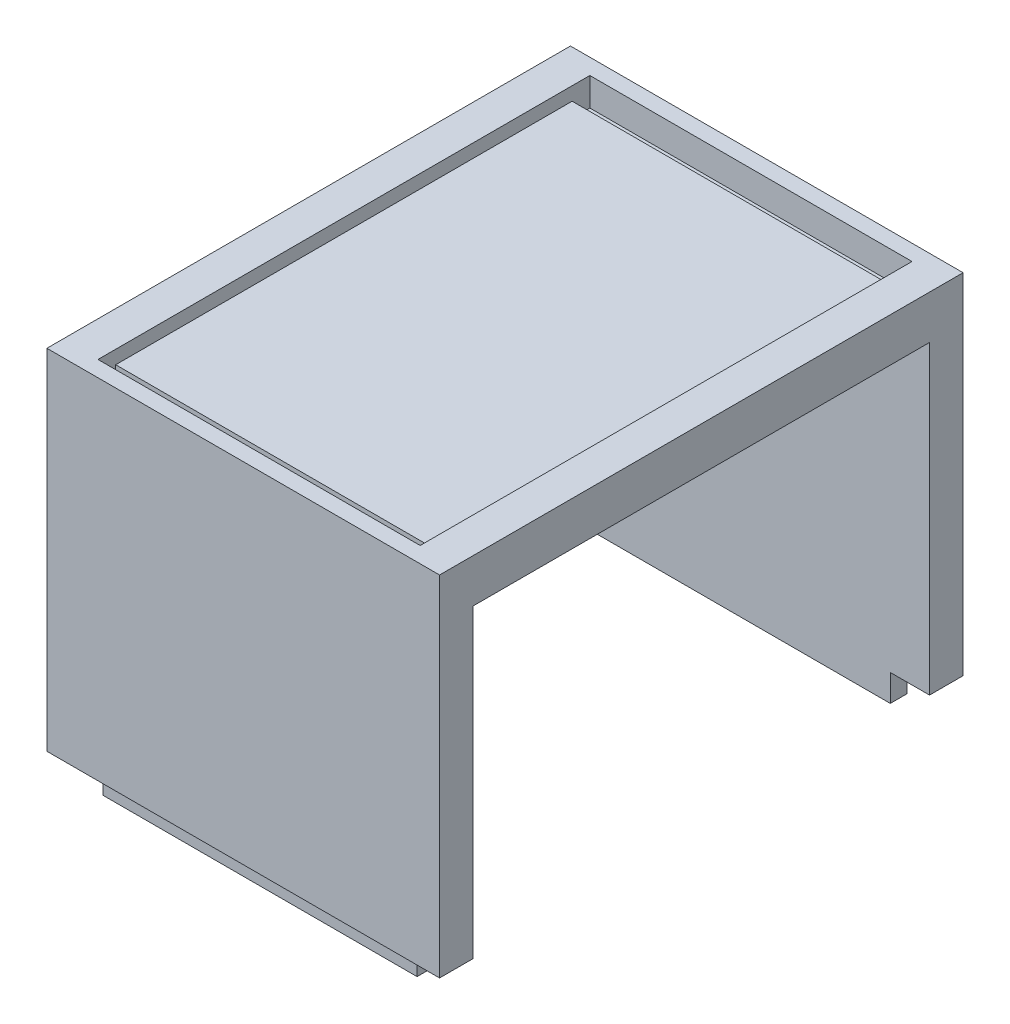
SolidWorks part; units mm, degrees
ref_plane "Front Plane" through (0, 0, 0) normal (0, 0, 1) x (1, 0, 0)
ref_plane "Top Plane" through (0, 0, 0) normal (0, 1, 0) x (1, 0, 0)
ref_plane "Right Plane" through (0, 0, 0) normal (1, 0, 0) x (0, 0, -1)
sketch "Sketch1" plane through (0, 0, 0) normal (0, 1, 0) x (1, 0, 0)
  line L1 (-14.625, 19.5) -> (14.625, 19.5)
  line L2 (-14.625, 19.5) -> (-14.625, -19.5)
  line L3 (-14.625, -19.5) -> (14.625, -19.5)
  line L4 (14.625, 19.5) -> (14.625, -19.5)
  line L5 (-14.625, 19.5) -> (14.625, -19.5) construction
  line L6 (-14.625, -19.5) -> (14.625, 19.5) construction
  point P0 (0, 0)
  dimension "D1" = 29.25
  dimension "D2" = 39
extrude "Boss-Extrude1" add sketch "Sketch1" along normal blind 3.25
sketch "Sketch2" plane through (0, 3.25, 0) normal (0, 1, 0) x (1, 0, 0)
  line L1 (-12, 17) -> (12, 17)
  line L2 (-12, 17) -> (-12, -17)
  line L3 (-12, -17) -> (12, -17)
  line L4 (12, 17) -> (12, -17)
  line L5 (-12, 17) -> (12, -17) construction
  line L6 (-12, -17) -> (12, 17) construction
  point P0 (0, 0)
  dimension "D1" = 24
  dimension "D2" = 34
extrude "Cut-Extrude1" cut sketch "Sketch2" against normal blind 1
sketch "Sketch3" plane through (0, 3.25, 0) normal (0, 1, 0) x (1, 0, 0)
  line L0 (-12, -17) -> (12, -17) construction
  line L1 (-12, -17) -> (12, -17)
  line L2 (-12, -17) -> (-12, -18.32)
  line L3 (-12, -18.32) -> (12, -18.32)
  line L4 (12, -17) -> (12, -18.32)
  line L5 (-12, -17) -> (12, -18.32) construction
  line L6 (-12, -18.32) -> (12, -17) construction
  line L7 (-12, 17) -> (-12, -17) construction
  point P0 (0, -17.66)
  dimension "D1" = 1.32
extrude "Cut-Extrude2" cut sketch "Sketch3" against normal blind 2.1
mirror "Mirror1" about plane through (0, 0, 0) normal (0, 0, 1) of "Cut-Extrude2"
sketch "Sketch4" plane through (0, 0, 19.5) normal (0, 0, 1) x (1, 0, 0)
  line L0 (-14.625, 0) -> (14.625, 0) construction
  line L1 (-14.625, 0) -> (14.625, 0)
  line L2 (-14.625, 0) -> (-14.625, -22.75)
  line L3 (-14.625, -22.75) -> (14.625, -22.75)
  line L4 (14.625, 0) -> (14.625, -22.75)
  line L5 (-14.625, 0) -> (14.625, -22.75) construction
  line L6 (-14.625, -22.75) -> (14.625, 0) construction
  line L7 (-14.625, 3.25) -> (-14.625, 0) construction
  point P0 (0, -11.375)
  dimension "D1" = 22.75
extrude "Boss-Extrude2" add sketch "Sketch4" against normal blind 2.5
sketch "Sketch6" plane through (0, -22.75, 0) normal (0, -1, 0) x (1, 0, 0)
  line L0 (-14.625, 17) -> (14.625, 17) construction
  line L1 (-11.7, 18.25) -> (11.7, 18.25)
  line L2 (-11.7, 18.25) -> (-11.7, 17)
  line L3 (-11.7, 17) -> (11.7, 17)
  line L4 (11.7, 18.25) -> (11.7, 17)
  line L5 (-11.7, 18.25) -> (11.7, 17) construction
  line L6 (-11.7, 17) -> (11.7, 18.25) construction
  point P0 (0, 17.625)
  dimension "D1" = 1.25
  dimension "D2" = 23.4
extrude "Boss-Extrude3" add sketch "Sketch6" along normal blind 2
mirror "Mirror2" about plane through (0, 0, 0) normal (0, 0, 1) of "Boss-Extrude3", "Boss-Extrude2"
